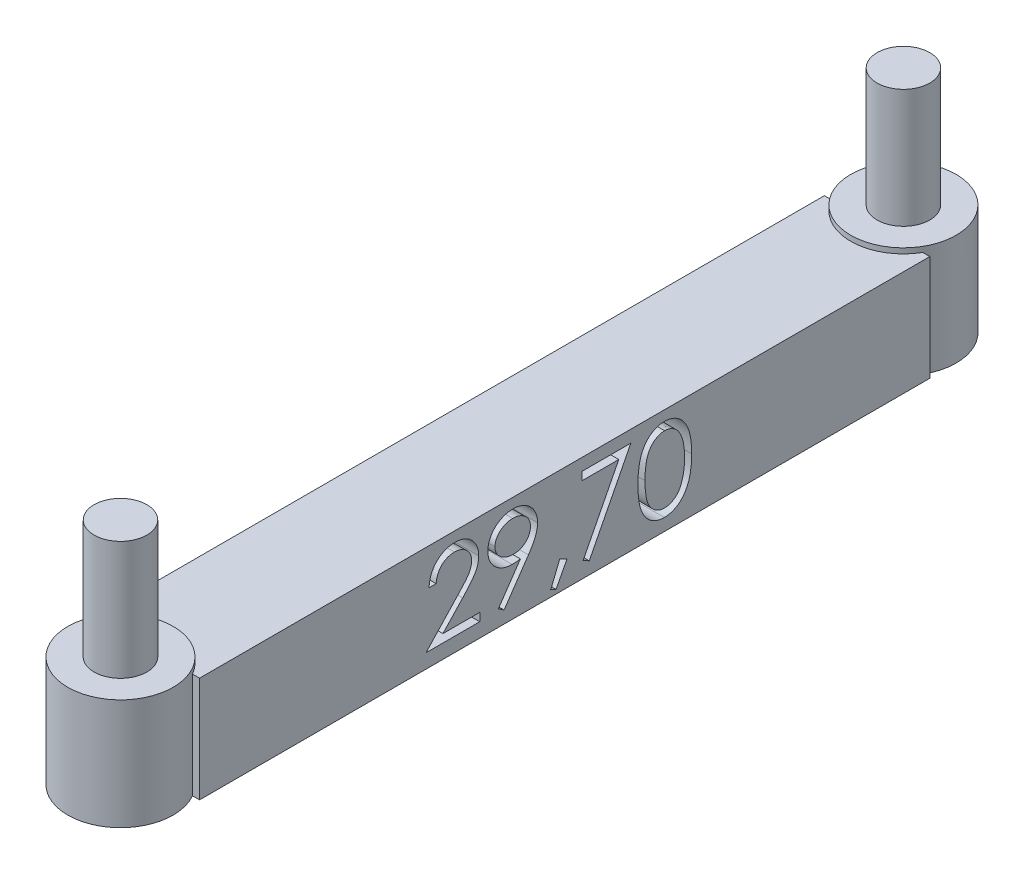
SolidWorks part; units mm, degrees
ref_plane "Ebene vorne" through (0, 0, 0) normal (0, 0, 1) x (1, 0, 0)
ref_plane "Ebene oben" through (0, 0, 0) normal (0, 1, 0) x (1, 0, 0)
ref_plane "Ebene rechts" through (0, 0, 0) normal (1, 0, 0) x (0, 0, -1)
sketch "Skizze1" plane through (0, 0, 0) normal (0, 0, 1) x (1, 0, 0)
  line L1 (-2, 2) -> (2, 2)
  line L2 (-2, 2) -> (-2, -2)
  line L3 (-2, -2) -> (2, -2)
  line L4 (2, 2) -> (2, -2)
  line L5 (-2, 2) -> (2, -2) construction
  line L6 (-2, -2) -> (2, 2) construction
  point P0 (0, 0)
  dimension "D1" = 4
  dimension "D2" = 4
extrude "Aufsatz-Linear austragen1" add sketch "Skizze1" along normal blind 27.7
sketch "Skizze2" plane through (0, 0, 0) normal (0, 1, 0) x (1, 0, 0)
  line L0 (0, -27.7) -> (0, 0) construction
  line L1 (2, -27.7) -> (-2, -27.7) construction
  circle A0 centre (0, -28.7) radius 2
  circle A2 centre (0, 1) radius 2
  point P9 (0, -13.85)
  dimension "D1" = 14.85
  dimension "D2" = 14.85
extrude "Aufsatz-Linear austragen2" add sketch "Skizze2" against normal blind 4 and the other way blind 0.2 from offset 2
sketch "Skizze3" plane through (0, 2.2, 0) normal (0, 1, 0) x (1, 0, 0)
  circle A0 centre (0, -28.7) radius 1
  circle A2 centre (0, 1) radius 1
extrude "Aufsatz-Linear austragen4" add sketch "Skizze3" along normal blind 4.5
fillet "Verrundung1" [suppressed] radius 2
sketch "Skizze4" plane through (2, 0, 0) normal (1, 0, 0) x (0, 0, -1)
  text T0 "29,70" font "Century Gothic" height 3
extrude "Schnitt-Linear austragen2" cut sketch "Skizze4" against normal blind 1
